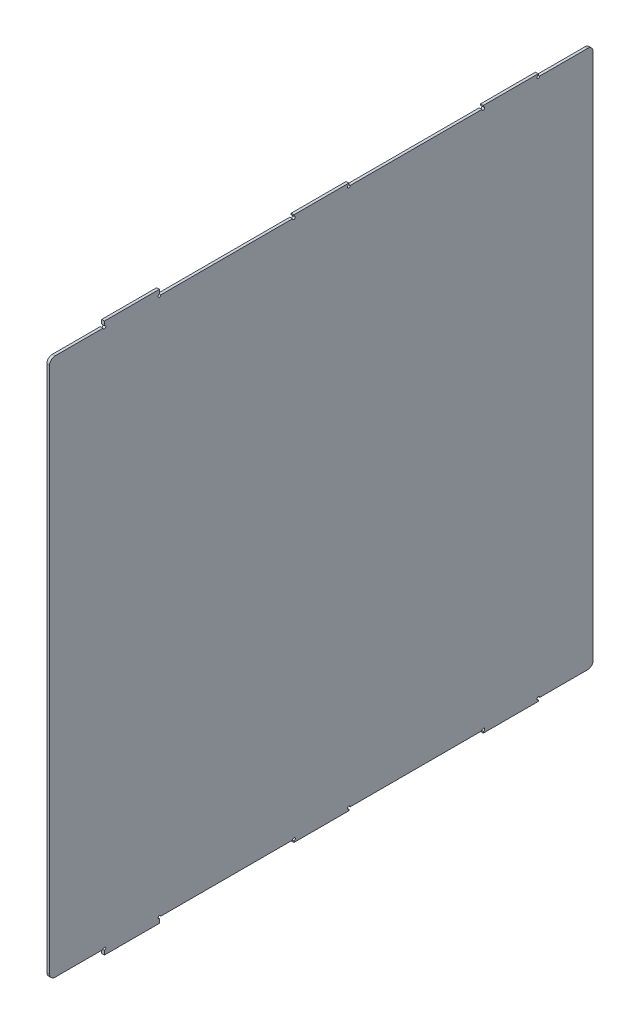
SolidWorks part; units mm, degrees
material "ASTM A36 Acier"
ref_plane "Front" through (0, 0, 0) normal (0, 0, 1) x (1, 0, 0)
ref_plane "Top" through (0, 0, 0) normal (0, 1, 0) x (1, 0, 0)
ref_plane "Right" through (0, 0, 0) normal (1, 0, 0) x (0, 0, -1)
sketch "Esquisse1" plane through (0, 0, 0) normal (1, 0, 0) x (0, 0, -1)
  line L0 (0, 0) -> (0, 99) construction
  line L2 (-99, -96) -> (-99, 96)
  line L3 (-97, 98) -> (-79, 98)
  line L4 (99, -96) -> (99, 96)
  line L5 (79, 98) -> (97, 98)
  line L6 (-59, 98) -> (-10, 98)
  line L8 (79, 98) -> (79, 99)
  line L9 (79, 99) -> (59, 99)
  line L10 (59, 98) -> (59, 99)
  line L12 (-10, 98) -> (-10, 99)
  line L13 (-10, 99) -> (10, 99)
  line L14 (10, 98) -> (10, 99)
  line L16 (-79, 98) -> (-79, 100)
  line L17 (-79, 100) -> (-59, 100)
  line L18 (-59, 98) -> (-59, 100)
  line L19 (10, 98) -> (59, 98)
  line L20 (-36.171, 0) -> (-50036.171, 0) construction
  line L22 (-59, -98) -> (-59, -100)
  line L23 (-79, -100) -> (-59, -100)
  line L24 (-79, -98) -> (-79, -100)
  line L26 (10, -98) -> (10, -99)
  line L27 (-10, -99) -> (10, -99)
  line L28 (-10, -98) -> (-10, -99)
  line L29 (59, -98) -> (59, -99)
  line L30 (79, -99) -> (59, -99)
  line L31 (79, -98) -> (79, -99)
  line L33 (-97, -98) -> (-79, -98)
  line L35 (-59, -98) -> (-10, -98)
  line L36 (10, -98) -> (59, -98)
  line L38 (79, -98) -> (97, -98)
  arc A2 (97, 98) -> (99, 96) centre (97, 96) cw
  arc A3 (-99, 96) -> (-97, 98) centre (-97, 96) cw
  arc A4 (-99, -96) -> (-97, -98) centre (-97, -96) ccw
  arc A5 (97, -98) -> (99, -96) centre (97, -96) ccw
  point P0 (0, 0)
  dimension "D11" = 2
  dimension "D2" = 198
  dimension "D3" = 20
  dimension "D4" = 1
  dimension "D5" = 20
  dimension "D6" = 1
  dimension "D7" = 20
  dimension "D8" = 20
  dimension "D9" = 20
  dimension "D10" = 2
  dimension "D12" = 196
  dimension "D13" = 99
base flange "Tôle de base pliée1" sketch "Esquisse1" thickness 1 reverse thickness direction no parameters "D1"=0.7366
sketch "Esquisse2" plane through (-1, 0, 0) normal (-1, 0, 0) x (0, 0, 1)
  line L12 (-99, 98) -> (-151.518, -98)
  line L13 (79, 98) -> (97, 98) construction
  line L14 (-99, -96) -> (-99, 96) construction
  line L15 (-151.518, -98) -> (-99, -98)
  line L16 (-99, -98) -> (-99, 98)
  line L17 (97, -98) -> (79, -98) construction
  dimension "D1" = 15
base flange "Patte1" [suppressed] sketch "Esquisse2" thickness 1 reverse thickness direction no parameters "D1"=0.7366
sketch "Esquisse3" plane through (0, 0, 0) normal (1, 0, 0) x (0, 0, -1)
  line L0 (0, 0) -> (50000, 0) construction
  circle A0 centre (-79, 98) radius 0.5
  circle A1 centre (-59, 98) radius 0.5
  circle A2 centre (-10, 98) radius 0.5
  circle A3 centre (10, 98) radius 0.5
  circle A4 centre (59, 98) radius 0.5
  circle A5 centre (79, 98) radius 0.5
  circle A6 centre (79, -98) radius 0.5
  circle A7 centre (59, -98) radius 0.5
  circle A8 centre (10, -98) radius 0.5
  circle A9 centre (-10, -98) radius 0.5
  circle A10 centre (-59, -98) radius 0.5
  circle A11 centre (-79, -98) radius 0.5
  dimension "D1" = 1
extrude "Enlèv. mat.-Extru.1" cut sketch "Esquisse3" against normal through all normal cut yes
sketch "Lignes de pliage1" [suppressed] plane through (0, 0, 0) normal (0, 1, 0) x (1, 0, 0)
sketch "Cube de visualisation1" [suppressed] plane through (0, 0, 0) normal (0, 1, 0) x (1, 0, 0)
sheet metal parameters "Tôlerie1" thickness 1 parameters "D1"=0.7366
flat pattern "Etat déplié1" [suppressed]
sketch "Lignes de pliage2" plane through (0, 0, 0) normal (0, 1, 0) x (1, 0, 0)
sketch3d "Cube de visualisation2" [suppressed]
  line L0 (-2, 4, 0) -> (-2, -196, 0) construction
  line L1 (196, 4, 0) -> (196, -196, 0) construction
  line L2 (-2, 4, 0) -> (196, 4, 0) construction
  line L3 (-2, -196, 0) -> (196, -196, 0) construction
sheet metal parameters "Tôlerie2" thickness 1 parameters "D1"=0.7366
flat pattern "Etat déplié2"
sketch "Lignes de pliage3" plane through (0, 0, 0) normal (0, 1, 0) x (1, 0, 0)
sketch3d "Cube de visualisation3" [suppressed]
  line L0 (152.0539, -99, 0) -> (-99, -99, 0) construction
  line L1 (152.0539, 99, 0) -> (-99, 99, 0) construction
  line L2 (152.0539, -99, 0) -> (152.0539, 99, 0) construction
  line L3 (-99, -99, 0) -> (-99, 99, 0) construction
sheet metal parameters "Tôlerie3" thickness 1 parameters "D1"=0.7366, "D7"=2
flat pattern "Etat déplié1"
sketch "Lignes de pliage2" plane through (0, 0, 0) normal (0, 1, 0) x (1, 0, 0)
sketch3d "Cube de visualisation2" [suppressed]
  line L0 (-2, -196, 0) -> (-2, 4, 0) construction
  line L1 (196, -196, 0) -> (196, 4, 0) construction
  line L2 (-2, -196, 0) -> (196, -196, 0) construction
  line L3 (-2, 4, 0) -> (196, 4, 0) construction
